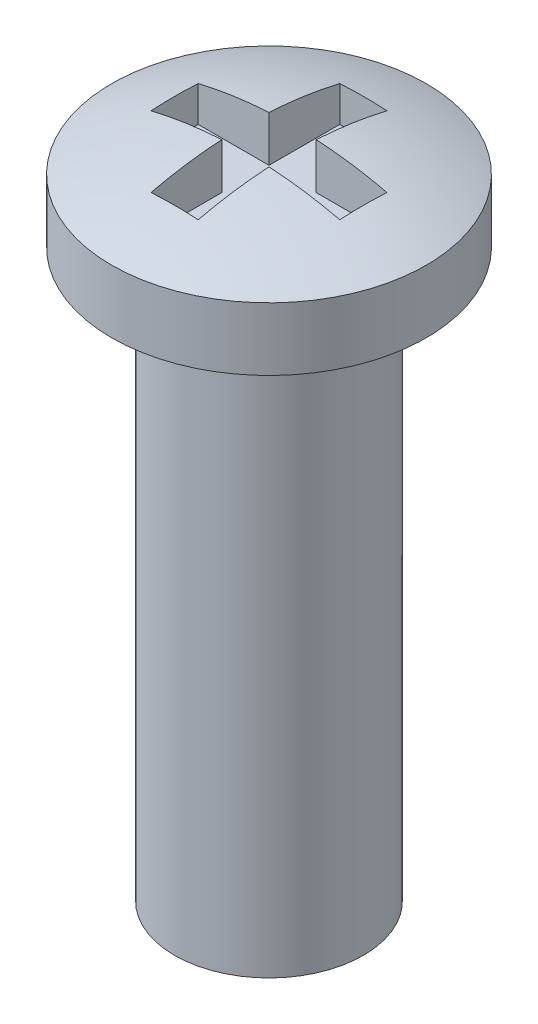
SolidWorks part; units mm, degrees
material "1023 Carbon Steel Sheet (SS)"
ref_plane "Front Plane" through (0, 0, 0) normal (0, 0, 1) x (1, 0, 0)
ref_plane "Top Plane" through (0, 0, 0) normal (0, 1, 0) x (1, 0, 0)
ref_plane "Right Plane" through (0, 0, 0) normal (1, 0, 0) x (0, 0, -1)
ref_plane "Top Plane1" through (0, 10.5, 0) normal (0, 1, 0) x (1, 0, 0)
sketch "Sketch1" plane through (0, 0, 0) normal (0, 1, 0) x (1, 0, 0)
  circle A0 centre (0, 0) radius 1.5
  dimension "D1" = 3
extrude "Boss-Extrude1" add sketch "Sketch1" along normal blind 9
sketch "Sketch2" plane through (0, 9, 0) normal (0, 1, 0) x (1, 0, 0)
  circle A0 centre (0, 0) radius 2.5
  dimension "D1" = 5
extrude "Boss-Extrude2" add sketch "Sketch2" along normal blind 1
dome "Dome1" faces to dome 1 distance 0.5 reverse direction no elliptical dome no face at (0, 10, 2.5) parameters "D1"=0.5
sketch "Sketch3" plane through (0, 10.5, 0) normal (0, 1, 0) x (1, 0, 0)
  line L0 (-2.5, 0) -> (2.5, 0) construction
  line L1 (0, 2.5) -> (0, -2.5) construction
  line L2 (-1.5, 0.375) -> (1.5, -0.375) construction
  line L3 (-1.5, 0.375) -> (1.5, 0.375)
  line L4 (-1.5, 0.375) -> (-1.5, -0.375)
  line L5 (-1.5, -0.375) -> (1.5, -0.375)
  line L6 (1.5, 0.375) -> (1.5, -0.375)
  line L7 (0.375, 1.5) -> (-0.375, -1.5) construction
  line L8 (-0.375, 1.5) -> (0.375, 1.5)
  line L9 (-0.375, 1.5) -> (-0.375, -1.5)
  line L10 (-0.375, -1.5) -> (0.375, -1.5)
  line L11 (0.375, 1.5) -> (0.375, -1.5)
  circle A0 centre (0, 0) radius 2.5 construction
  dimension "D1" = 1.5
  dimension "D2" = 1.5
  dimension "D3" = 0.75
  dimension "D4" = 0.75
extrude "Cut-Extrude1" cut sketch "Sketch3" against normal blind 0.75 contours L9 L3 L4 L5 | L11 L3 L9 L5 | L11 L8 L9 L3 | L3 L11 L5 L6 | L11 L5 L9 L10 region at (-0.9375, 10.5, 0) region at (0, 10.5, -0.9375) region at (0, 10.5, 0) region at (0.9375, 10.5, 0) region at (0, 10.5, 0.9375)
sketch "Sketch4" plane through (0, 0, 0) normal (0, -1, 0) x (1, 0, 0)
  point P0 (0, 0)
